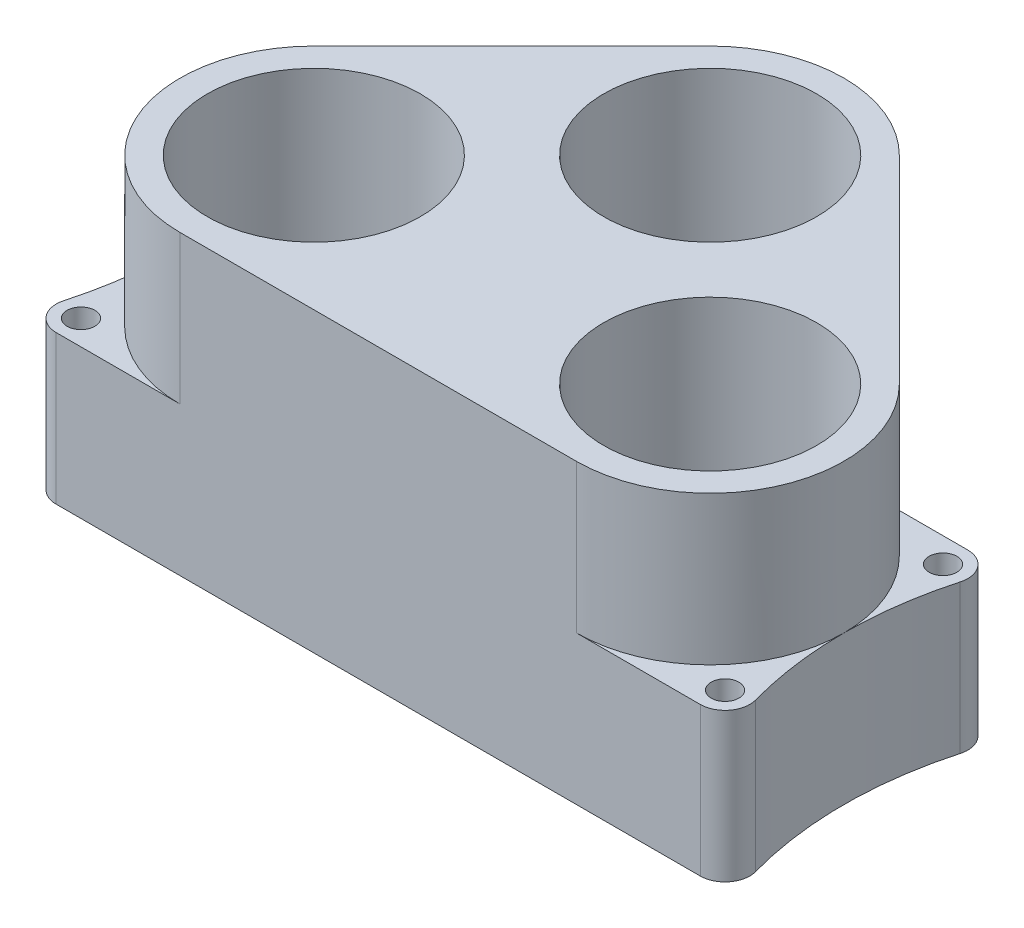
SolidWorks part; units mm, degrees
note: The reader was unsure of these and kept them because the rebuilt part matched: shared geometry of "Sketch1<3>".
ref_plane "Front Plane" through (0, 0, 0) normal (0, 0, 1) x (1, 0, 0)
ref_plane "Top Plane" through (0, 0, 0) normal (0, 1, 0) x (1, 0, 0)
ref_plane "Right Plane" through (0, 0, 0) normal (1, 0, 0) x (0, 0, -1)
sketch "Sketch1" plane through (0, 0, 0) normal (0, 1, 0) x (1, 0, 0)
  line L0 (0, 0) -> (101.6, 0) construction
  line L1 (0, 34.29) -> (101.6, 34.29)
  line L2 (0, -34.29) -> (101.6, -34.29)
  line L3 (0, -34.29) -> (-31.75, -34.29)
  line L4 (50.8, 0) -> (50.8, 11.8344) construction
  line L5 (101.6, -34.29) -> (133.35, -34.29)
  line L6 (50.8, 0) -> (80.4411, 0) construction
  line L7 (101.6, 34.29) -> (133.35, 34.29)
  line L8 (0, 34.29) -> (-31.75, 34.29)
  line L9 (-24.2467, 24.2467) -> (26.5533, 75.0467)
  line L10 (75.0467, 75.0467) -> (125.8467, 24.2467)
  circle A0 centre (0, 0) radius 27.305
  circle A2 centre (101.6, 0) radius 27.305
  arc A3 (0, 34.29) -> (0, -34.29) centre (0, 0) ccw
  arc A4 (101.6, -34.29) -> (101.6, 34.29) centre (101.6, 0) ccw
  arc A5 (-31.75, -34.29) -> (-37.8682, -26.2398) centre (-31.75, -27.94) cw
  arc A6 (-37.8682, -26.2398) -> (-37.8682, 26.2398) centre (-132.2917, 0) ccw
  circle A7 centre (-31.75, -27.94) radius 3.556
  arc A8 (139.4682, -26.2398) -> (139.4682, 26.2398) centre (233.8917, 0) cw
  circle A9 centre (133.35, -27.94) radius 3.556
  arc A10 (133.35, -34.29) -> (139.4682, -26.2398) centre (133.35, -27.94) ccw
  arc A11 (133.35, 34.29) -> (139.4682, 26.2398) centre (133.35, 27.94) cw
  circle A12 centre (133.35, 27.94) radius 3.556
  circle A13 centre (-31.75, 27.94) radius 3.556
  arc A14 (-31.75, 34.29) -> (-37.8682, 26.2398) centre (-31.75, 27.94) ccw
  circle A15 centre (50.8, 0) radius 27.305 [skipped]
  arc A16 (26.5533, 75.0467) -> (75.0467, 75.0467) centre (50.8, 50.8) cw
  circle A17 centre (50.8, 50.8) radius 27.305
  point P4 (50.8, 0)
  dimension "D1" = 54.61
  dimension "D4" = 34.29
  dimension "D5" = 7.112
  dimension "D6" = 55.88
  dimension "D3" = 101.6
  dimension "D7" = 165.1
  dimension "D8" = 50.8
  dimension "D2" = 3
extrude "Boss-Extrude1" add sketch "Sketch1" along normal blind 76.2
extrude "Boss-Extrude2" add sketch "Sketch1<3>" along normal blind 38.1 contours A6 A5 L3 A3 A7 | L5 A10 A8 A4 A9 | A11 L7 A4 A8 A12 | L8 A14 A6 A3 A13
sketch "Sketch1<3>" plane through (0, 0, 0) normal (0, 1, 0) x (1, 0, 0) same geometry as "Sketch1"
